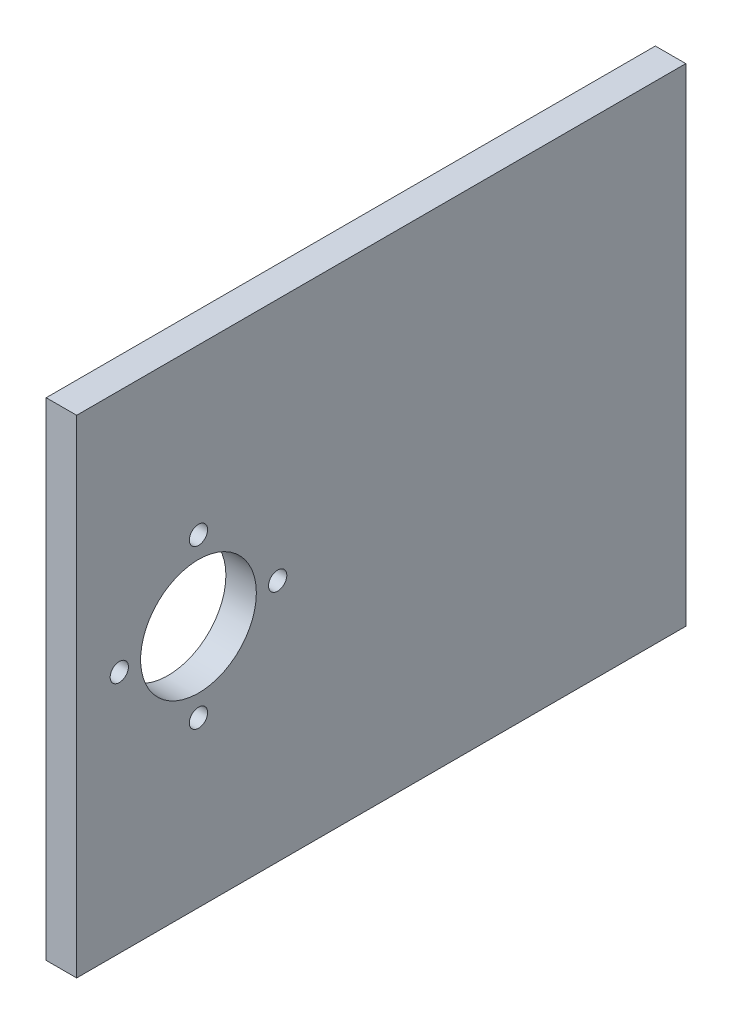
SolidWorks part; units mm, degrees
ref_plane "Front Plane" through (0, 0, 0) normal (1, 0, 0) x (0, 1, 0)
ref_plane "Top Plane" through (0, 0, 0) normal (0, 0, 1) x (0, 1, 0)
ref_plane "Right Plane" through (0, 0, 0) normal (0, 1, 0) x (-1, 0, 0)
sketch "Sketch1" plane through (0, 0, 0) normal (1, 0, 0) x (0, 1, 0)
  line L0 (0, 50) -> (0, -50) construction
  line L1 (-40, -50) -> (40, -50)
  line L2 (-40, -50) -> (-40, 50)
  line L3 (-40, 50) -> (40, 50)
  line L4 (40, -50) -> (40, 50)
  line L5 (-40, -50) -> (40, 50) construction
  line L6 (-40, 50) -> (40, -50) construction
  line L7 (-40, 30) -> (40, 30) construction
  circle A1 centre (0, 43) radius 1.5
  circle A2 centre (0, 17) radius 1.5
  circle A3 centre (-13, 30) radius 1.5
  circle A4 centre (13, 30) radius 1.5
  circle A5 centre (0, 30) radius 9.5
  point P0 (0, 0)
  dimension "D5" = 3
  dimension "D6" = 3
  dimension "D7" = 13
  dimension "D8" = 19
  dimension "D1" = 80
  dimension "D2" = 100
  dimension "D3" = 80
  dimension "D4" = 13
extrude "Boss-Extrude1" add sketch "Sketch1" along normal blind 5
